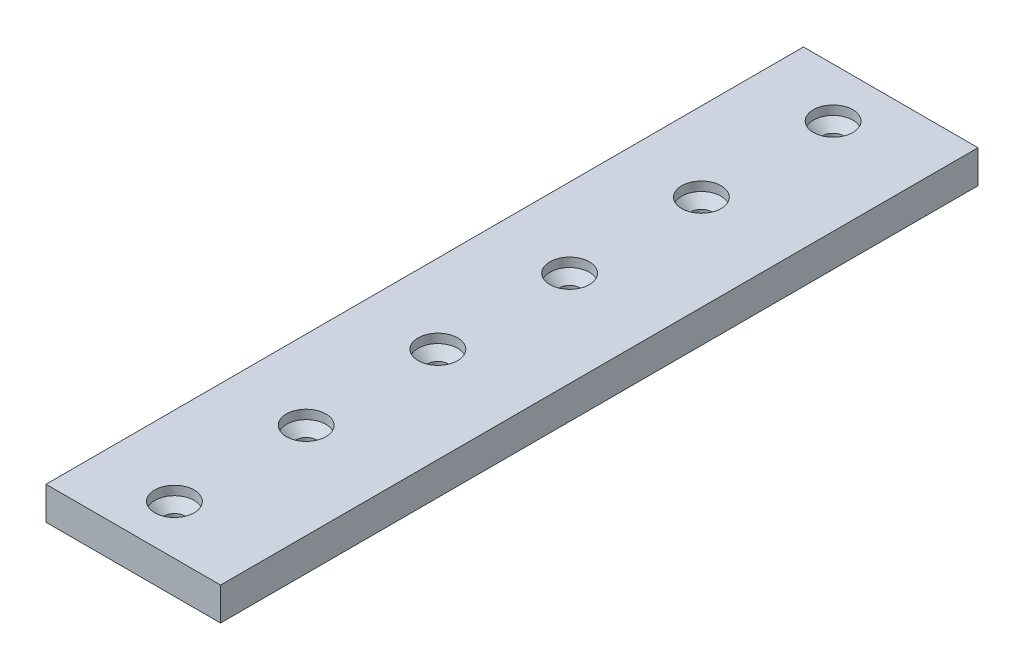
SolidWorks part; units mm, degrees
ref_plane "Front Plane" through (0, 0, 0) normal (0, 0, 1) x (1, 0, 0)
ref_plane "Top Plane" through (0, 0, 0) normal (0, 1, 0) x (1, 0, 0)
ref_plane "Right Plane" through (0, 0, 0) normal (1, 0, 0) x (0, 0, -1)
sketch "Sketch1" plane through (0, 0, 0) normal (0, 0, 1) x (1, 0, 0)
  line L1 (-24, -24) -> (24, -24)
  line L2 (-24, -24) -> (-24, 24)
  line L3 (-24, 24) -> (24, 24)
  line L4 (24, -24) -> (24, 24)
  line L5 (-24, -24) -> (24, 24) construction
  line L6 (-24, 24) -> (24, -24) construction
  line L7 (24, -24) -> (29, -24)
  line L8 (24, -24) -> (24, 35.2)
  line L9 (24, 35.2) -> (29, 35.2)
  line L10 (29, -24) -> (29, 35.2)
  line L11 (24, 35.2) -> (-24, 35.2)
  line L12 (24, 35.2) -> (24, 25.2)
  line L13 (24, 25.2) -> (-24, 25.2)
  line L14 (-24, 35.2) -> (-24, 25.2)
  circle A0 centre (0, 0) radius 13.75
  dimension "D1" = 27.5
  dimension "D2" = 1.2
  dimension "D3" = 48
  dimension "D4" = 48
  dimension "D5" = 5
  dimension "D6" = 10
extrude "Boss-Extrude1" add sketch "Sketch1" along normal blind 230 contours L1 L4 L3 L2 A0 | L11 L14 L13 L8 | L7 L10 L9 L8 L4 region at (-23.3212, 0, 0) region at (26.5, 5.6, 0) region at (0, 30.2, 0)
sketch "Sketch3" plane through (0, 35.2, 0) normal (0, 1, 0) x (1, 0, 0)
  line L0 (0, 0) -> (0, -230) construction
  line L1 (-24, -230) -> (29, -230) construction
  circle A0 centre (0, -15) radius 6
  circle A1 centre (0, -55) radius 6
  circle A2 centre (0, -95) radius 6
  circle A3 centre (0, -135) radius 6
  circle A4 centre (0, -175) radius 6
  circle A5 centre (0, -215) radius 6
  dimension "D1" = 12
  dimension "D2" = 15
  dimension "D4" = 15
  dimension "D3" = 6
extrude "Cut-Extrude1" cut sketch "Sketch3" against normal blind 0.5
sketch "Sketch4" plane through (0, 35.2, 0) normal (0, 1, 0) x (1, 0, 0)
  line L0 (0, 0) -> (0, -230) construction
  line L1 (-24, -230) -> (29, -230) construction
  circle A0 centre (0, -15) radius 3.25
  circle A1 centre (0, -55) radius 3.25
  circle A2 centre (0, -95) radius 3.25
  circle A3 centre (0, -135) radius 3.25
  circle A4 centre (0, -175) radius 3.25
  circle A5 centre (0, -215) radius 3.25
  dimension "D1" = 6.5
  dimension "D2" = 6
extrude "Cut-Extrude2" cut sketch "Sketch4" against normal through all
sketch "Sketch5" plane through (0, -24, 0) normal (0, -1, 0) x (1, 0, 0)
  line L0 (0, 230) -> (0, 0) construction
  line L1 (-24, 230) -> (29, 230) construction
  circle A0 centre (0, 215) radius 6.5
  circle A1 centre (0, 175) radius 6.5
  circle A2 centre (0, 135) radius 6.5
  circle A3 centre (0, 95) radius 6.5
  circle A4 centre (0, 55) radius 6.5
  circle A5 centre (0, 15) radius 6.5
  dimension "D1" = 13
  dimension "D2" = 6
extrude "Cut-Extrude3" cut sketch "Sketch5" against normal up to next
sketch "Sketch7" plane through (0, 24, 0) normal (0, 1, 0) x (1, 0, 0)
  line L0 (0, 0) -> (0, -230) construction
  line L1 (0, -8.5337) -> (-5.6, -11.7668)
  line L2 (-5.6, -11.7668) -> (-5.6, -18.2332)
  line L3 (-5.6, -18.2332) -> (0, -21.4663)
  line L4 (0, -21.4663) -> (5.6, -18.2332)
  line L5 (5.6, -18.2332) -> (5.6, -11.7668)
  line L6 (5.6, -11.7668) -> (0, -8.5337)
  line L7 (-24, -230) -> (29, -230) construction
  line L8 (0, -48.5337) -> (-5.6, -51.7668)
  line L9 (-5.6, -51.7668) -> (-5.6, -58.2332)
  line L10 (-5.6, -58.2332) -> (0, -61.4663)
  line L11 (0, -61.4663) -> (5.6, -58.2332)
  line L12 (5.6, -58.2332) -> (5.6, -51.7668)
  line L13 (5.6, -51.7668) -> (0, -48.5337)
  line L14 (0, -88.5337) -> (-5.6, -91.7668)
  line L15 (-5.6, -91.7668) -> (-5.6, -98.2332)
  line L16 (-5.6, -98.2332) -> (0, -101.4663)
  line L17 (0, -101.4663) -> (5.6, -98.2332)
  line L18 (5.6, -98.2332) -> (5.6, -91.7668)
  line L19 (5.6, -91.7668) -> (0, -88.5337)
  line L20 (0, -128.5337) -> (-5.6, -131.7668)
  line L21 (-5.6, -131.7668) -> (-5.6, -138.2332)
  line L22 (-5.6, -138.2332) -> (0, -141.4663)
  line L23 (0, -141.4663) -> (5.6, -138.2332)
  line L24 (5.6, -138.2332) -> (5.6, -131.7668)
  line L25 (5.6, -131.7668) -> (0, -128.5337)
  line L26 (0, -168.5337) -> (-5.6, -171.7668)
  line L27 (-5.6, -171.7668) -> (-5.6, -178.2332)
  line L28 (-5.6, -178.2332) -> (0, -181.4663)
  line L29 (0, -181.4663) -> (5.6, -178.2332)
  line L30 (5.6, -178.2332) -> (5.6, -171.7668)
  line L31 (5.6, -171.7668) -> (0, -168.5337)
  line L32 (0, -208.5337) -> (-5.6, -211.7668)
  line L33 (-5.6, -211.7668) -> (-5.6, -218.2332)
  line L34 (-5.6, -218.2332) -> (0, -221.4663)
  line L35 (0, -221.4663) -> (5.6, -218.2332)
  line L36 (5.6, -218.2332) -> (5.6, -211.7668)
  line L37 (5.6, -211.7668) -> (0, -208.5337)
  circle A0 centre (0, -15) radius 5.6 construction
  dimension "D1" = 11.2
  dimension "D2" = 6
extrude "Cut-Extrude4" cut sketch "Sketch7" against normal up to next from offset 5 offset against normal yes
chamfer "Chamfer1" distance 5 angle 45 6 edges at (0, 34.7, 218.25) (0, 34.7, 178.25) (0, 34.7, 138.25) (0, 34.7, 98.25) (0, 34.7, 58.25) (0, 34.7, 18.25)
sketch "Sketch8" plane through (24, 0, 0) normal (-1, 0, 0) x (0, 0, 1)
  line L1 (0, 25.2) -> (230, 25.2)
  line L2 (0, 25.2) -> (0, 24)
  line L3 (0, 24) -> (230, 24)
  line L4 (230, 25.2) -> (230, 24)
extrude "Cut-Extrude5" cut sketch "Sketch8" against normal blind 10
